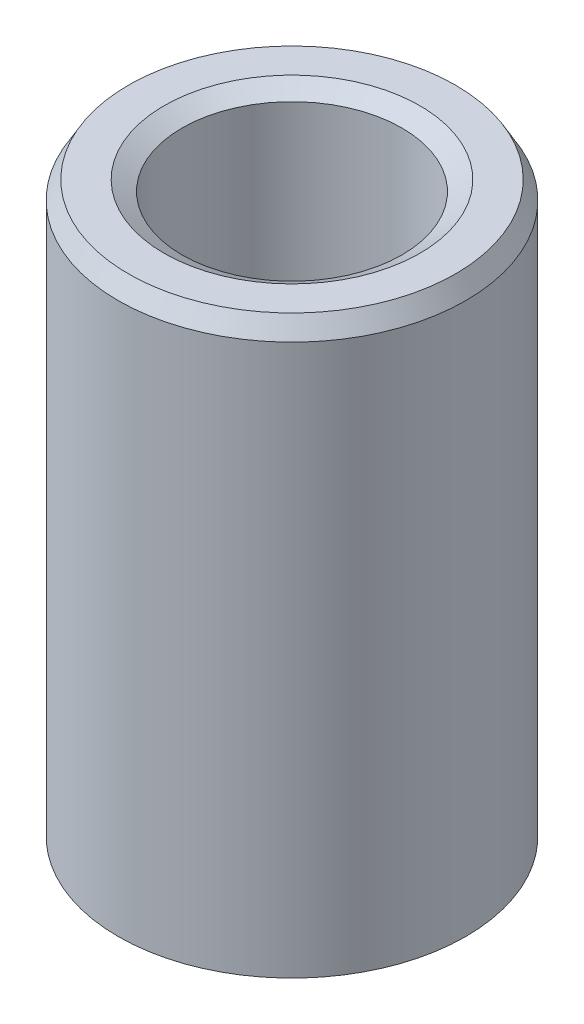
SolidWorks part; units mm, degrees
ref_plane "Front Plane" through (0, 0, 0) normal (0, 0, 1) x (1, 0, 0)
ref_plane "Top Plane" through (0, 0, 0) normal (0, 1, 0) x (1, 0, 0)
ref_plane "Right Plane" through (0, 0, 0) normal (1, 0, 0) x (0, 0, -1)
sketch "Sketch1" plane through (0, 0, 0) normal (0, 1, 0) x (1, 0, 0)
  circle A0 centre (0, 0) radius 37.5
  dimension "SLEEVE_OD" = 75
extrude "Boss-Extrude1" add sketch "Sketch1" along normal blind 124.8818
sketch "Sketch2" plane through (0, 0, 0) normal (0, 1, 0) x (1, 0, 0)
  circle A0 centre (0, 0) radius 23.7161
  dimension "BORE_D" = 47.4323
extrude "Cut-Extrude1" cut sketch "Sketch2" along normal through all
chamfer "Chamfer1" distance 3.8668 angle 30 4 edges at (0, 124.8818, 23.7161) (0, 0, 23.7161) (0, 0, 37.5) (0, 124.8818, 37.5) first distance on face at (0, 124.8818, 23.7161) first distance on face at (0, 0, 23.7161) first distance on face at (0, 124.8818, 37.5)
